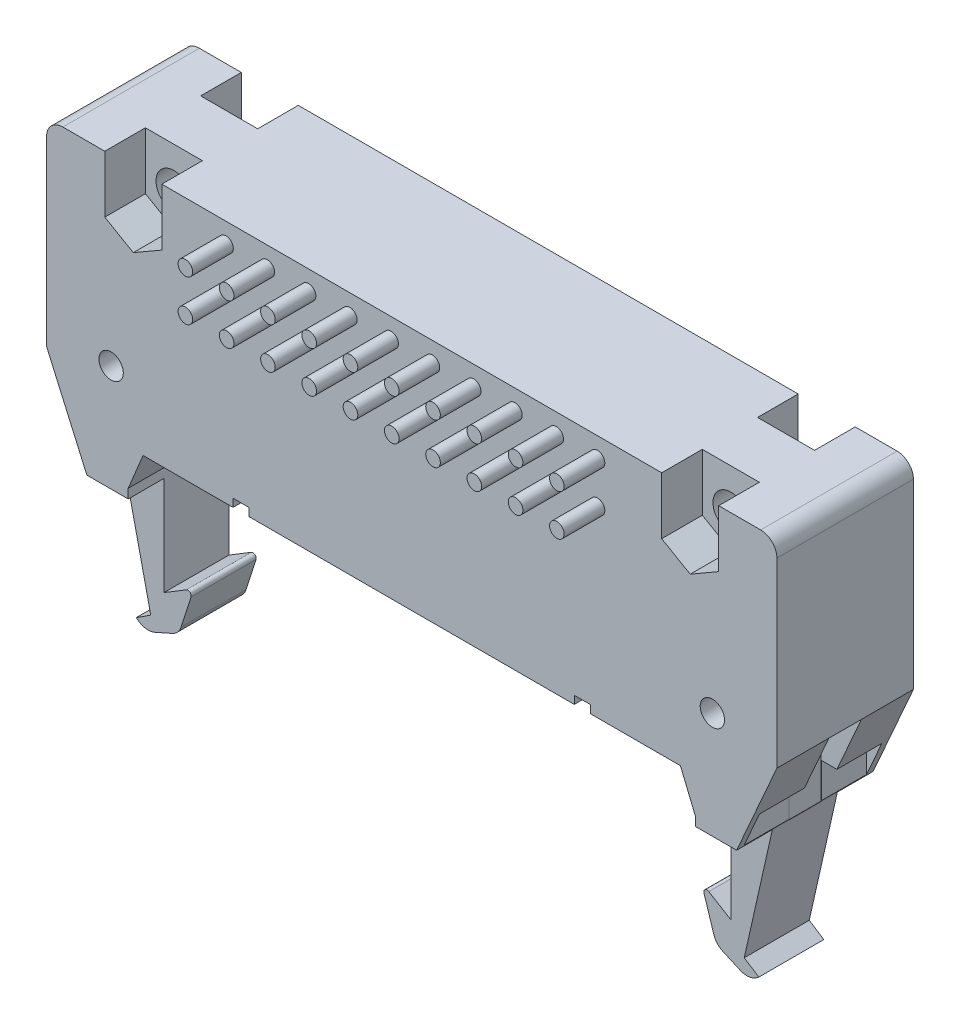
SolidWorks part; units mm, degrees
ref_plane "Спереди" through (0, 0, 0) normal (0, 0, 1) x (1, 0, 0)
ref_plane "Сверху" through (0, 0, 0) normal (0, 1, 0) x (1, 0, 0)
ref_plane "Справа" through (0, 0, 0) normal (1, 0, 0) x (0, 0, -1)
sketch "Эскиз1" plane through (0, 0, 0) normal (0, 0, 1) x (1, 0, 0)
  line L0 (0, 8.2919) -> (0, -18.517) construction
  line L1 (49.2464, 0) -> (-43.5201, 0) construction
  line L2 (-17.4461, -11.8582) -> (-16.5322, -9.653)
  line L3 (-16.5322, -9.653) -> (16.5322, -9.653)
  line L4 (-17.4461, -18.517) -> (-17.4461, -11.8582)
  line L5 (-21.47, 5.3815) -> (21.47, 5.3815)
  line L6 (22.47, -6.8161) -> (22.47, 4.3815)
  line L7 (-19.9906, -12.4303) -> (-22.47, -6.8161)
  line L8 (17.4461, -18.517) -> (16.0759, -17.6849)
  line L9 (15.7816, -17.9169) -> (16.3951, -19.8329)
  line L10 (16.9435, -20.4427) -> (18.0209, -20.9185)
  line L11 (19.0186, -20.8085) -> (19.1561, -20.707)
  line L12 (19.1561, -20.707) -> (18.2604, -20.1256)
  line L13 (18.2604, -20.1256) -> (19.9906, -12.4303)
  line L14 (19.9906, -12.4303) -> (22.47, -6.8161)
  line L15 (17.4461, -18.517) -> (17.4461, -11.8582)
  line L16 (17.4461, -11.8582) -> (16.5322, -9.653)
  line L17 (-18.2604, -20.1256) -> (-19.9906, -12.4303)
  line L18 (-19.1561, -20.707) -> (-18.2604, -20.1256)
  line L19 (-19.0186, -20.8085) -> (-19.1561, -20.707)
  line L20 (-16.9435, -20.4427) -> (-18.0209, -20.9185)
  line L21 (-15.7816, -17.9169) -> (-16.3951, -19.8329)
  line L22 (-17.4461, -18.517) -> (-16.0759, -17.6849)
  line L23 (-22.47, -6.8161) -> (-22.47, 4.3815)
  arc A0 (16.3951, -19.8329) -> (16.9435, -20.4427) centre (17.3475, -19.5279) ccw
  arc A1 (18.0209, -20.9185) -> (19.0186, -20.8085) centre (18.4249, -20.0038) ccw
  arc A2 (16.0759, -17.6849) -> (15.7816, -17.9169) centre (15.9721, -17.8559) ccw
  arc A3 (21.47, 5.3815) -> (22.47, 4.3815) centre (21.47, 4.3815) cw
  arc A4 (-21.47, 5.3815) -> (-22.47, 4.3815) centre (-21.47, 4.3815) ccw
  arc A5 (-16.0759, -17.6849) -> (-15.7816, -17.9169) centre (-15.9721, -17.8559) cw
  arc A6 (-18.0209, -20.9185) -> (-19.0186, -20.8085) centre (-18.4249, -20.0038) cw
  arc A7 (-16.3951, -19.8329) -> (-16.9435, -20.4427) centre (-17.3475, -19.5279) cw
  point P27 (0, 5.3815)
  point P45 (0, -9.653)
  dimension "D1" = 22.47
extrude "Вытянуть1" add sketch "Эскиз1" along normal blind 8.4
sketch "Эскиз2" plane through (22.47, 0, 0) normal (1, 0, 0) x (0, 0, -1)
  line L0 (-4.2, 8.0464) -> (-4.2, -24.3467) construction
  line L4 (-10.0759, -23.066) -> (-6.2, -23.066)
  line L5 (-10.0759, -23.066) -> (-10.0759, -12.4303)
  line L6 (-10.0759, -12.4303) -> (-6.2, -12.4303)
  line L7 (-6.2, -23.066) -> (-6.2, -12.4303)
  line L8 (-2.2, -23.066) -> (-2.2, -12.4303)
  line L9 (1.6759, -12.4303) -> (-2.2, -12.4303)
  line L10 (1.6759, -23.066) -> (1.6759, -12.4303)
  line L11 (1.6759, -23.066) -> (-2.2, -23.066)
  line L12 (-8.4, -12.4303) -> (0, -12.4303) construction
  dimension "D1" = 2
extrude "Вырез-Вытянуть1" cut sketch "Эскиз2" against normal blind 150
sketch "Эскиз3" plane through (22.47, 0, 0) normal (1, 0, 0) x (0, 0, -1)
  line L0 (-4.2, -21.7791) -> (-4.2, -1.2196) construction
  line L4 (-5.2, -12.4303) -> (-3.2, -12.4303)
  line L5 (-5.2, -12.4303) -> (-5.2, -6.8161)
  line L6 (-5.2, -6.8161) -> (-3.2, -6.8161)
  line L7 (-3.2, -12.4303) -> (-3.2, -6.8161)
  line L9 (-8.4, -6.8161) -> (-8.4, 4.3815) construction
  line L10 (0, -6.8161) -> (0, 4.3815) construction
  line L11 (-8.4, -6.8161) -> (0, -6.8161) construction
  line L12 (-8.4, -12.4303) -> (-6.2, -12.4303) construction
  dimension "D1" = 2
extrude "Вырез-Вытянуть2" cut sketch "Эскиз3" against normal blind 2.5
sketch "Эскиз4" plane through (22.47, 0, 0) normal (1, 0, 0) x (0, 0, -1)
  line L0 (-4.2, -13.7122) -> (-4.2, -4.7037) construction
  line L4 (-7.9666, -12.4303) -> (-0.4334, -12.4303)
  line L5 (-7.9666, -12.4303) -> (-7.9666, -10.2303)
  line L6 (-7.9666, -10.2303) -> (-0.4334, -10.2303)
  line L7 (-0.4334, -12.4303) -> (-0.4334, -10.2303)
  line L8 (-8.4, -12.4303) -> (-8.4, -6.8161) construction
  line L9 (0, -12.4303) -> (0, -6.8161) construction
  line L10 (-8.4, -12.4303) -> (-6.2, -12.4303) construction
  dimension "D1" = 2.2
extrude "Вырез-Вытянуть3" cut sketch "Эскиз4" against normal offset from surface (2.45 mm away) 0.05 up to face at (19.97, -9.6232, 4.2)
sketch "Эскиз5" plane through (-22.47, 0, 0) normal (-1, 0, 0) x (0, 0, 1)
  line L4 (5.2, -12.4303) -> (5.2, -6.8161)
  line L5 (3.2, -12.4303) -> (5.2, -12.4303)
  line L6 (3.2, -6.8161) -> (3.2, -12.4303)
  line L7 (5.2, -6.8161) -> (3.2, -6.8161)
  line L8 (5.2, -12.4303) -> (5.2, -6.8161)
  line L9 (3.2, -12.4303) -> (5.2, -12.4303)
  line L10 (3.2, -6.8161) -> (3.2, -12.4303)
  line L11 (5.2, -6.8161) -> (3.2, -6.8161)
  dimension "D1" = 0
extrude "Вырез-Вытянуть4" cut sketch "Эскиз5" against normal blind 2.5
sketch "Эскиз6" plane through (-22.47, 0, 0) normal (-1, 0, 0) x (0, 0, 1)
  line L4 (5.2, -10.2303) -> (5.2, -12.3637)
  line L5 (7.9666, -10.2303) -> (5.2, -10.2303)
  line L6 (7.9666, -12.3637) -> (7.9666, -10.2303)
  line L7 (5.2, -12.3637) -> (7.9666, -12.3637)
  line L8 (5.2, -10.2303) -> (5.2, -12.3637)
  line L9 (7.9666, -10.2303) -> (5.2, -10.2303)
  line L10 (7.9666, -12.3637) -> (7.9666, -10.2303)
  line L11 (5.2, -12.3637) -> (7.9666, -12.3637)
  line L12 (0.4334, -10.2303) -> (0.4334, -12.3637)
  line L13 (3.2, -10.2303) -> (0.4334, -10.2303)
  line L14 (3.2, -12.3637) -> (3.2, -10.2303)
  line L15 (0.4334, -12.3637) -> (3.2, -12.3637)
  line L16 (0.4334, -10.2303) -> (0.4334, -12.3637)
  line L17 (3.2, -10.2303) -> (0.4334, -10.2303)
  line L18 (3.2, -12.3637) -> (3.2, -10.2303)
  line L19 (0.4334, -12.3637) -> (3.2, -12.3637)
  dimension "D1" = 0
  dimension "D2" = 0
extrude "Вырез-Вытянуть5" cut sketch "Эскиз6" against normal offset from surface (2.45 mm away) 0.05 up to face at (-19.97, -9.6232, 4.2)
sketch "Эскиз7" plane through (0, -9.653, 0) normal (0, -1, 0) x (1, 0, 0)
  line L0 (-16.9344, 4.2) -> (17.0384, 4.2) construction
  line L4 (-16.5322, 1.45) -> (16.5322, 1.45)
  line L5 (-16.5322, 1.45) -> (-16.5322, 6.95)
  line L6 (-16.5322, 6.95) -> (16.5322, 6.95)
  line L7 (16.5322, 1.45) -> (16.5322, 6.95)
  line L8 (-16.5322, 8.4) -> (-16.5322, 0) construction
  line L9 (16.5322, 8.4) -> (16.5322, 0) construction
  dimension "D1" = 5.5
extrude "Вырез-Вытянуть6" cut sketch "Эскиз7" against normal blind 10
sketch "Эскиз8" plane through (0, 0.347, 0) normal (0, -1, 0) x (1, 0, 0)
  line L0 (-5.9309, 4.2) -> (6.6853, 4.2) construction
  line L3 (16.5322, 6.95) -> (-16.5322, 6.95) construction
  line L4 (-16.5322, 1.45) -> (16.5322, 1.45) construction
  circle A0 centre (6.35, 2.93) radius 0.45
  circle A1 centre (6.35, 5.47) radius 0.45
  circle A2 centre (1.27, 5.47) radius 0.45
  circle A3 centre (1.27, 2.93) radius 0.45
  circle A4 centre (3.81, 5.47) radius 0.45
  circle A5 centre (3.81, 2.93) radius 0.45
  circle A6 centre (-1.27, 5.47) radius 0.45
  circle A7 centre (-1.27, 2.93) radius 0.45
  circle A8 centre (-3.81, 5.47) radius 0.45
  circle A9 centre (-3.81, 2.93) radius 0.45
  circle A10 centre (-1.27, 2.93) radius 0.45 [skipped]
  circle A11 centre (1.27, 2.93) radius 0.45 [skipped]
  circle A12 centre (-1.27, 5.47) radius 0.45 [skipped]
  circle A13 centre (1.27, 5.47) radius 0.45 [skipped]
  circle A14 centre (8.89, 2.93) radius 0.45
  circle A15 centre (8.89, 5.47) radius 0.45
  circle A16 centre (11.43, 2.93) radius 0.45
  circle A17 centre (11.43, 5.47) radius 0.45
  circle A18 centre (-6.35, 5.47) radius 0.45
  circle A19 centre (-6.35, 2.93) radius 0.45
  circle A20 centre (-8.89, 5.47) radius 0.45
  circle A21 centre (-8.89, 2.93) radius 0.45
  circle A22 centre (-11.43, 5.47) radius 0.45
  circle A23 centre (-11.43, 2.93) radius 0.45
  dimension "D1" = 2.54
  dimension "D2" = 2.54
  dimension "D3" = 3.81
  dimension "D4" = 3.81
  dimension "D5" = 0.9
extrude "Вытянуть2" add sketch "Эскиз8" along normal blind 8
sketch "Эскиз9" plane through (0, 0, 0) normal (0, 0, -1) x (-1, 0, 0)
  line L0 (0, 7.8731) -> (0, -14.2295) construction
  line L4 (-17.135, 2.8815) -> (17.135, 2.8815) construction
  line L5 (-19.3588, -5.8676) -> (4.9318, -5.8676) construction
  line L6 (10, -10.1387) -> (10, -9.1642)
  line L7 (-11, -10.1387) -> (-10, -10.1387)
  line L8 (-11, -10.1387) -> (-11, -9.1642)
  line L9 (-11, -9.1642) -> (-10, -9.1642)
  line L10 (-10, -10.1387) -> (-10, -9.1642)
  line L11 (11, -9.1642) -> (10, -9.1642)
  line L12 (11, -10.1387) -> (11, -9.1642)
  line L13 (11, -10.1387) -> (10, -10.1387)
  line L14 (-22.47, -6.8161) -> (-22.47, 4.3815) construction
  line L15 (22.47, 4.3815) -> (22.47, -6.8161) construction
  circle A0 centre (-17.135, 2.8815) radius 1.1
  circle A1 centre (17.135, 2.8815) radius 1.1
  circle A2 centre (-18.5, -5.8676) radius 0.75
  circle A3 centre (18.5, -5.8676) radius 0.75
  dimension "D1" = 34.27
  dimension "D2" = 20
  dimension "D3" = 2.2
  dimension "D4" = 1.5
  dimension "D5" = 18.5
  dimension "D6" = 1
extrude "Вырез-Вытянуть7" cut sketch "Эскиз9" against normal blind 10
sketch "Эскиз10" plane through (0, 0, 0) normal (0, 0, -1) x (-1, 0, 0)
  line L0 (0, -4.0596) -> (0, 7.1047) construction
  line L1 (-18.8894, 3.9876) -> (-18.8894, 6.5566)
  line L2 (-18.8894, 6.5566) -> (-15.3806, 6.5566)
  line L3 (-18.8894, 3.9876) -> (-18.8894, 1.8685)
  line L4 (-18.8894, 1.8685) -> (-17.135, 0.8556)
  line L5 (-17.135, 0.8556) -> (-15.3806, 1.8685)
  line L6 (-15.3806, 1.8685) -> (-15.3806, 3.9876)
  line L7 (-15.3806, 6.5566) -> (-15.3806, 3.9876)
  line L8 (-17.5548, 4.665) -> (-18.432, 4.1585) [skipped]
  line L9 (-15.8811, 4.1834) -> (-16.7583, 4.6898) [skipped]
  line L10 (15.3806, 6.5566) -> (15.3806, 3.9876)
  line L11 (15.3806, 1.8685) -> (15.3806, 3.9876)
  line L12 (17.135, 0.8556) -> (15.3806, 1.8685)
  line L13 (18.8894, 1.8685) -> (17.135, 0.8556)
  line L14 (18.8894, 3.9876) -> (18.8894, 1.8685)
  line L15 (18.8894, 6.5566) -> (15.3806, 6.5566)
  line L16 (18.8894, 3.9876) -> (18.8894, 6.5566)
  line L17 (-17.135, 0.8556) -> (-17.135, 5.3815) construction
  line L20 (-14.5, 1.8685) -> (14.5, 1.8685)
  line L21 (-14.5, 1.8685) -> (-14.5, 3.8685)
  line L22 (-14.5, 3.8685) -> (14.5, 3.8685)
  line L23 (14.5, 1.8685) -> (14.5, 3.8685)
  circle A0 centre (-17.135, 2.8815) radius 1.7544 construction
  circle A1 centre (17.135, 2.8815) radius 1.7544 construction
  dimension "D1" = 2
  dimension "D2" = 34.27
  dimension "D3" = 29
extrude "Вырез-Вытянуть8" cut sketch "Эскиз10" against normal blind 2.5
sketch "Эскиз11" plane through (0, 0, 8.4) normal (0, 0, 1) x (1, 0, 0)
  line L5 (18.8894, 1.8685) -> (18.8894, 5.3815)
  line L6 (17.135, 0.8556) -> (18.8894, 1.8685)
  line L7 (15.3806, 1.8685) -> (17.135, 0.8556)
  line L8 (15.3806, 5.3815) -> (15.3806, 1.8685)
  line L9 (18.8894, 5.3815) -> (15.3806, 5.3815)
  line L10 (18.8894, 1.8685) -> (18.8894, 5.3815)
  line L11 (17.135, 0.8556) -> (18.8894, 1.8685)
  line L12 (15.3806, 1.8685) -> (17.135, 0.8556)
  line L13 (15.3806, 5.3815) -> (15.3806, 1.8685)
  line L14 (18.8894, 5.3815) -> (15.3806, 5.3815)
  line L15 (-15.3806, 5.3815) -> (-18.8894, 5.3815)
  line L16 (-15.3806, 5.3815) -> (-18.8894, 5.3815)
  line L24 (-15.3806, 1.8685) -> (-15.3806, 5.3815)
  line L25 (-17.135, 0.8556) -> (-15.3806, 1.8685)
  line L26 (-18.8894, 1.8685) -> (-17.135, 0.8556)
  line L27 (-18.8894, 5.3815) -> (-18.8894, 1.8685)
  line L29 (-15.3806, 1.8685) -> (-15.3806, 5.3815)
  line L30 (-17.135, 0.8556) -> (-15.3806, 1.8685)
  line L31 (-18.8894, 1.8685) -> (-17.135, 0.8556)
  line L32 (-18.8894, 5.3815) -> (-18.8894, 1.8685)
  dimension "D1" = 0
  dimension "D3" = 0
extrude "Вырез-Вытянуть9" cut sketch "Эскиз11" against normal blind 2.5
sketch "Эскиз12" plane through (0, 0, 0) normal (0, 0, -1) x (-1, 0, 0)
  line L0 (0, 0) -> (0, -11.6719) construction
  line L2 (-2.3, -10.95) -> (2.3, -10.95)
  line L3 (-2.3, -10.95) -> (-2.3, -1.653)
  line L4 (-2.3, -1.653) -> (2.3, -1.653)
  line L5 (2.3, -10.95) -> (2.3, -1.653)
  line L6 (10, -9.653) -> (-10, -9.653) construction
  dimension "D1" = 4.6
  dimension "D2" = 8
extrude "Вырез-Вытянуть10" cut sketch "Эскиз12" against normal up to surface (1.45 mm away) up to face at (0, -7.8234, 1.45)
chamfer "Фаска1" distance 2 angle 45 1 edges at (0, -1.653, 0)
sketch "Эскиз13" plane through (0, 0, 0) normal (0, 0, -1) x (-1, 0, 0)
  line L1 (13.5172, -9.653) -> (14.4807, -9.653)
  line L2 (16.5322, -9.653) -> (11, -9.653) construction
  line L3 (14.4807, -9.653) -> (13.9989, -8.8186)
  line L4 (13.9989, -8.8186) -> (13.5172, -9.653)
extrude "Вырез-Вытянуть11" cut sketch "Эскиз13" against normal blind 0.2
sketch "Эскиз14" plane through (0, 0, 8.4) normal (0, 0, 1) x (1, 0, 0)
  line L0 (-17.135, 2.8815) -> (10.9546, 2.8815) construction
  line L1 (0, -2.2554) -> (0, 5.0268) construction
  circle A0 centre (6.35, 4.1515) radius 0.45
  circle A1 centre (6.35, 1.6115) radius 0.45
  circle A2 centre (1.27, 4.1515) radius 0.45
  circle A3 centre (1.27, 1.6115) radius 0.45
  circle A4 centre (3.81, 4.1515) radius 0.45
  circle A5 centre (3.81, 1.6115) radius 0.45
  circle A6 centre (-1.27, 4.1515) radius 0.45
  circle A7 centre (-1.27, 1.6115) radius 0.45
  circle A8 centre (-3.81, 4.1515) radius 0.45
  circle A9 centre (-3.81, 1.6115) radius 0.45
  circle A10 centre (-1.27, 1.6115) radius 0.45 [skipped]
  circle A11 centre (1.27, 1.6115) radius 0.45 [skipped]
  circle A12 centre (-1.27, 4.1515) radius 0.45 [skipped]
  circle A13 centre (1.27, 4.1515) radius 0.45 [skipped]
  circle A14 centre (8.89, 4.1515) radius 0.45
  circle A15 centre (8.89, 1.6115) radius 0.45
  circle A16 centre (11.43, 4.1515) radius 0.45
  circle A17 centre (11.43, 1.6115) radius 0.45
  circle A18 centre (-6.35, 1.6115) radius 0.45
  circle A19 centre (-6.35, 4.1515) radius 0.45
  circle A20 centre (-8.89, 1.6115) radius 0.45
  circle A21 centre (-8.89, 4.1515) radius 0.45
  circle A22 centre (-11.43, 1.6115) radius 0.45
  circle A23 centre (-11.43, 4.1515) radius 0.45
  dimension "D1" = 2.54
  dimension "D2" = 2.54
extrude "Вытянуть3" add sketch "Эскиз14" along normal blind 2.5
